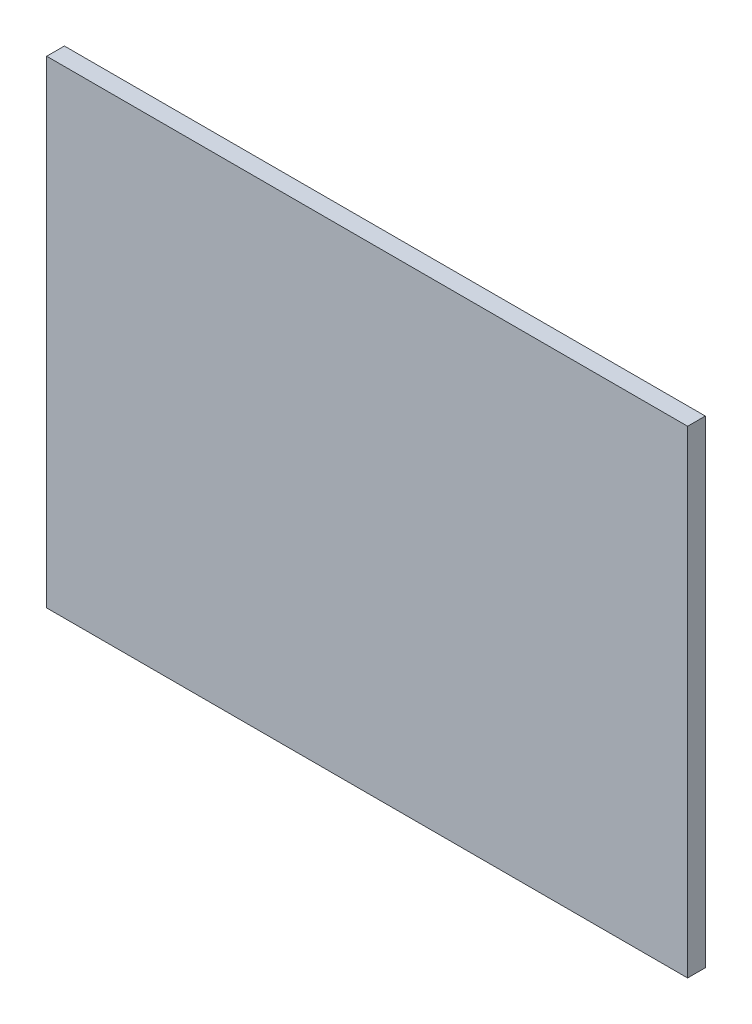
SolidWorks part; units mm, degrees
ref_plane "Front Plane" through (0, 0, 0) normal (0, 0, 1) x (1, 0, 0)
ref_plane "Top Plane" through (0, 0, 0) normal (0, 1, 0) x (1, 0, 0)
ref_plane "Right Plane" through (0, 0, 0) normal (1, 0, 0) x (0, 0, -1)
sketch "Sketch1" plane through (0, 0, 0) normal (0, 0, 1) x (1, 0, 0)
  line L0 (90.6195, -3.175) -> (90.6195, 3.175) construction
  line L1 (90.6195, -15.875) -> (-139.3499, -15.875)
  line L2 (90.6195, -15.875) -> (90.6195, 155.575)
  line L3 (90.6195, 155.575) -> (-139.3499, 155.575)
  line L4 (-139.3499, -15.875) -> (-139.3499, 155.575)
  line L5 (113.7824, 69.85) -> (-193.0608, 69.85) construction
  line L6 (90.6195, -3.175) -> (-26.6981, -3.175) construction
  line L7 (90.6195, 142.875) -> (-122.1584, 142.875) construction
  ellipse E0 centre (47.625, 171.7384) end of major axis (47.625, -44.1616) minor radius 186.9749 (190.7889, 310.6087) -> (-12.8669, 376.0269) ccw construction
  dimension "D1" = 12.7
extrude "Boss-Extrude1" add sketch "Sketch1" along normal blind 6.35
